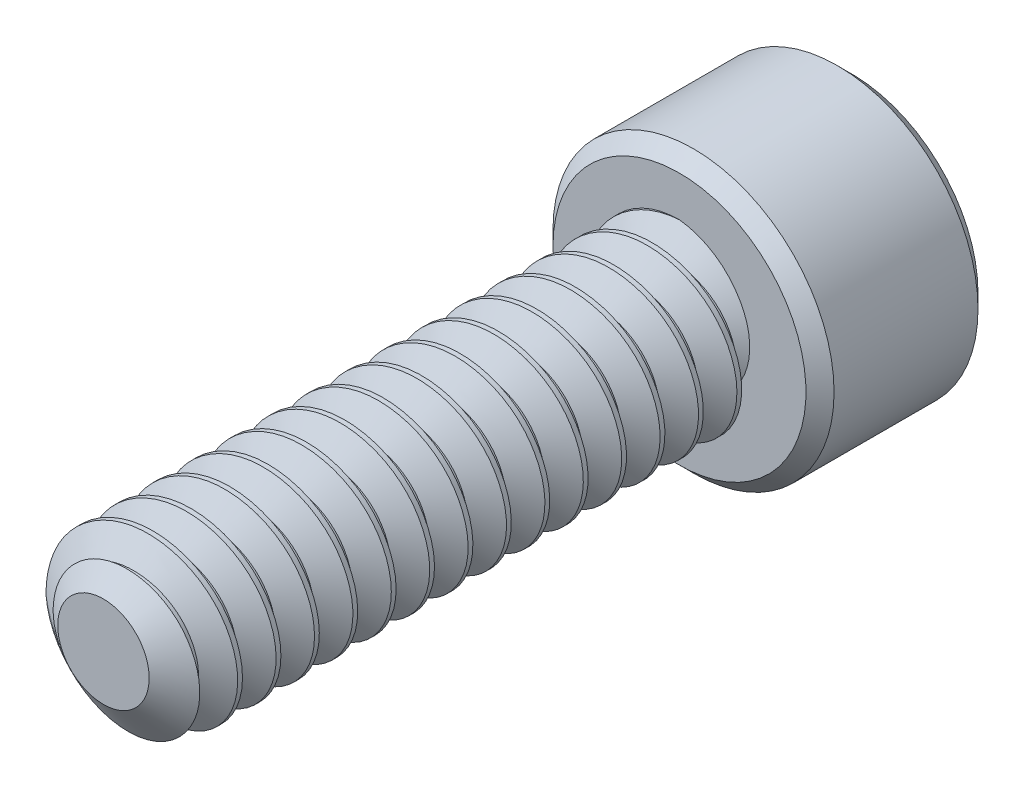
SolidWorks part; units mm, degrees
material "Alloy Steel"
ref_plane "Front Plane" through (0, 0, 0) normal (0, 0, 1) x (1, 0, 0)
ref_plane "Top Plane" through (0, 0, 0) normal (0, 1, 0) x (1, 0, 0)
ref_plane "Right Plane" through (0, 0, 0) normal (1, 0, 0) x (0, 0, -1)
sketch "Sketch1" plane through (0, 0, 0) normal (0, 0, 1) x (1, 0, 0)
  circle A0 centre (0, 0) radius 1.4224
  dimension "OD" = 2.8448
extrude "Extrude1" add sketch "Sketch1" against normal blind 9.525
sketch "Sketch2" plane through (0, 0, 0) normal (0, 0, 1) x (1, 0, 0)
  circle A0 centre (0, 0) radius 1.4224 construction
  circle A1 centre (0, 0) radius 1.4224
curve "Helix/Spiral1" pitch 0.635 height 10.16 turns 16 parameters "pitch"=0.635
sketch "Sketch3" plane through (0, 0, 0) normal (1, 0, 0) x (0, 0, -1)
  line L0 (-0.5556, 1.4224) -> (-0.3175, 1.01)
  line L1 (-0.3175, 1.01) -> (-0.2381, 1.01)
  line L2 (-0.2381, 1.01) -> (0, 1.4224)
  line L3 (-0.5556, 1.4224) -> (0, 1.4224)
  line L4 (-0.2778, 1.4224) -> (-0.2778, 1.01) construction
  line L5 (-0.4366, 1.2162) -> (-0.1191, 1.2162) construction
  line L6 (0, 1.4224) -> (0, -1.4224) construction
  dimension "D1" = 0.0794
  dimension "D2" = 0.3175
  dimension "D3" = 60
sweep "Cut-Sweep1" cut profiles "Sketch3" path "Helix/Spiral1"
sketch "Sketch4" plane through (0, 0, 0) normal (1, 0, 0) x (0, 0, -1)
  line L0 (0.4666, 1.4224) -> (0, 0.756)
  line L1 (0, 0.756) -> (0, 1.4224)
  line L2 (0.4666, 1.4224) -> (0, 1.4224)
  line L3 (-0.5556, 1.4224) -> (0, 1.4224) construction
  line L4 (0, 0) -> (7.0209, 0) construction
  dimension "D1" = 55
  dimension "D2" = 0.254
revolve "Cut-Revolve1" cut sketch "Sketch4" angle 360 about L4
sketch "Sketch5" plane through (0, 0, 0) normal (1, 0, 0) x (0, 0, -1)
  line L0 (9.525, -1.0232) -> (9.525, 1.0149) construction
  line L1 (9.525, 1.5494) -> (38.1885, 1.5494)
  line L2 (9.525, 1.5494) -> (9.525, 0)
  line L3 (9.525, 0) -> (38.1, 0)
  line L4 (38.1, 1.2192) -> (38.1, 0)
  line L5 (38.1885, 1.5494) -> (38.1, 1.2192)
  line L6 (0, 0) -> (9.9695, 0) construction
  point P3 (38.1, 1.5494)
  point P10 (38.1, 1.5494)
  dimension "D1" = 0.3302
  dimension "Thread min" = 38.1
  dimension "D2" = 0.127
  dimension "D3" = 15
revolve "partially thread" [suppressed] add sketch "Sketch5" angle 360 about L6
sketch "Sketch6" plane through (0, 0, -9.525) normal (0, 0, -1) x (-1, 0, 0)
  circle A0 centre (0, 0) radius 2.3241
  dimension "head dia" = 4.6482
extrude "Extrude2" add sketch "Sketch6" along normal blind 2.8448
sketch "Sketch7" plane through (0, 0, -12.3698) normal (0, 0, -1) x (-1, 0, 0)
  line L1 (0, 1.3748) -> (-1.1906, 0.6874)
  line L2 (-1.1906, 0.6874) -> (-1.1906, -0.6874)
  line L3 (-1.1906, -0.6874) -> (0, -1.3748)
  line L4 (0, -1.3748) -> (1.1906, -0.6874)
  line L5 (1.1906, -0.6874) -> (1.1906, 0.6874)
  line L6 (1.1906, 0.6874) -> (0, 1.3748)
  circle A0 centre (0, 0) radius 1.1906 construction
  dimension "hex dia" = 2.3813
extrude "Cut-Extrude1" cut sketch "Sketch7" against normal blind 1.7859
sketch "Sketch8" plane through (0, 0, -12.3698) normal (0, 0, -1) x (-1, 0, 0)
  circle A0 centre (0, 0) radius 1.3748
extrude "Cut-Extrude2" cut sketch "Sketch8" against normal through all draft 45
chamfer "Chamfer1" distance 0.2324 angle 45 2 edges at (-2.3241, 0, -12.3698) (-2.3241, 0, -9.525)
sketch "Sketch9" plane through (0, 0, 0) normal (1, 0, 0) x (0, 0, -1)
  line L0 (0, 1.4224) -> (0, -1.4224) construction
  line L1 (6.6675, 1.4224) -> (6.6675, -1.4224) construction
  dimension "D1" = 6.6675
  dimension "D4" = 0.635
  dimension "D5" = 0.3302
equation "\"D3@Helix/Spiral1\" = \"screw length@Extrude1\"+\"pitch@Helix/Spiral1\""
equation "\"D1@Sketch3\" = \"pitch@Helix/Spiral1\"*.125"
equation "\"D2@Sketch3\" = \"pitch@Helix/Spiral1\"*.5"
equation "\"D1@Cut-Extrude1\" = \"hex dia@Sketch7\"*.75"
equation "\"D1@Chamfer1\" = \"head dia@Sketch6\"*.05"
equation "\"D1@Sketch9\" = \"pitch@Helix/Spiral1\"*10.5"
